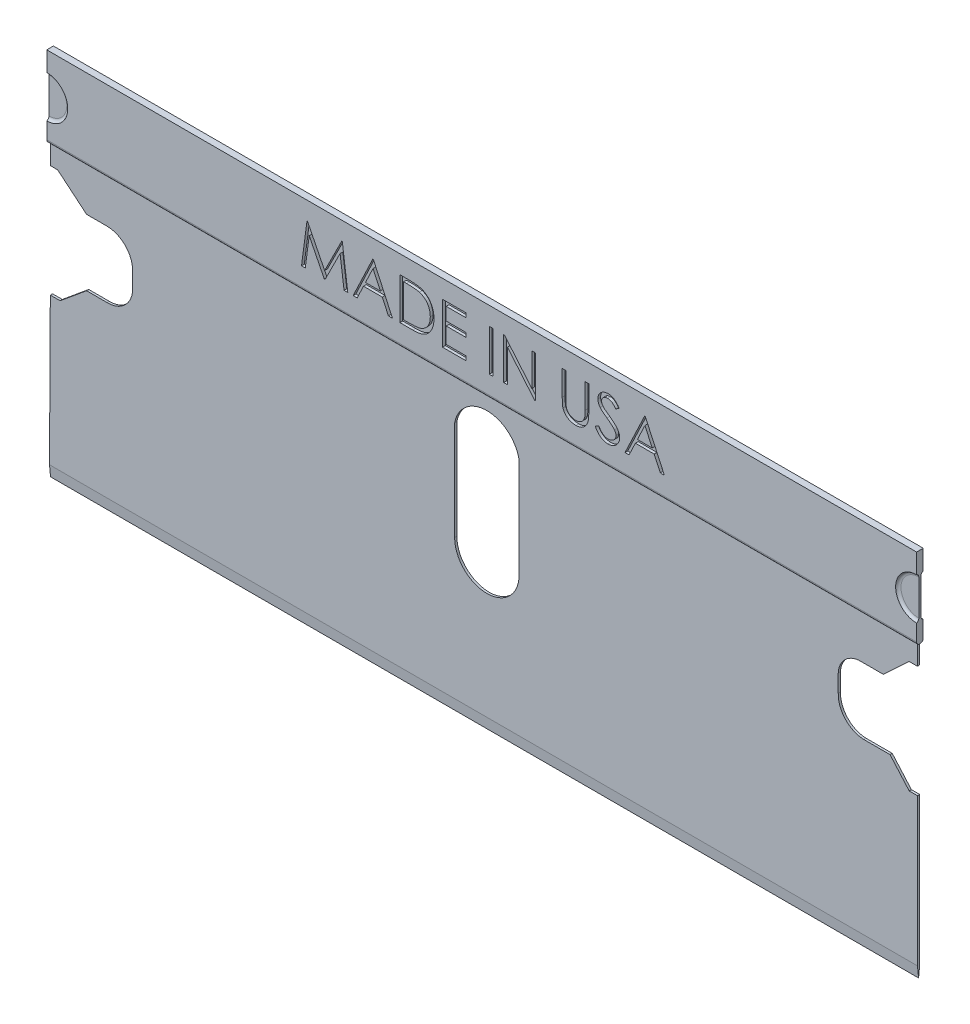
SolidWorks part; units mm, degrees
ref_plane "Front Plane" through (0, 0, 0) normal (0, 0, 1) x (1, 0, 0)
ref_plane "Top Plane" through (0, 0, 0) normal (0, 1, 0) x (1, 0, 0)
ref_plane "Right Plane" through (0, 0, 0) normal (1, 0, 0) x (0, 0, -1)
sketch "Sketch1" plane through (0, 0, 0) normal (0, 0, 1) x (1, 0, 0)
  line L0 (68.5, 98.5) -> (342.5, 98.5) construction
  line L1 (6.6432, 0) -> (405.0953, 0)
  line L2 (405.0953, 0) -> (405.0953, 72.7175)
  line L3 (392.4917, 82.7561) -> (380.4108, 82.7561)
  line L4 (368.7248, 95.2868) -> (368.7248, 103.2753)
  line L5 (379.511, 113.1269) -> (389.4487, 113.1269)
  line L6 (405.0953, 72.7175) -> (401.3011, 72.7175)
  line L7 (405.0953, 124.1749) -> (401.3011, 124.1749)
  line L8 (405.0953, 124.1749) -> (405.0953, 133.9462)
  line L9 (405.0953, 133.9462) -> (7.043, 133.9462)
  line L10 (7.043, 133.9462) -> (7.043, 124.1749)
  line L11 (7.043, 124.1749) -> (10.404, 124.1749)
  line L12 (23.6907, 113.1269) -> (33.0176, 113.1269)
  line L13 (44.8608, 101.2782) -> (44.8608, 93.9286)
  line L14 (33.0176, 82.7561) -> (23.6907, 82.7561)
  line L15 (10.404, 124.1749) -> (23.6907, 113.1269)
  line L16 (23.6907, 82.7561) -> (11.5392, 72.7175)
  line L17 (11.5392, 72.7175) -> (7.043, 72.7175)
  line L18 (7.043, 72.7175) -> (6.6432, 0)
  line L19 (192.6406, 114.6996) -> (192.6406, 69.1011)
  line L20 (222.2574, 114.6996) -> (222.2574, 69.1011)
  line L21 (401.3011, 124.1749) -> (389.4487, 113.1269)
  line L22 (401.3011, 72.7175) -> (392.4917, 82.7561)
  arc A0 (33.0176, 113.1269) -> (44.8608, 101.2782) centre (33.0176, 101.2838) cw
  arc A1 (380.4108, 82.7561) -> (368.7248, 95.2868) centre (380.8331, 94.8645) cw
  arc A2 (368.7248, 103.2753) -> (379.511, 113.1269) centre (379.0437, 102.8081) cw
  arc A3 (44.8608, 93.9286) -> (33.0176, 82.7561) centre (33.353, 94.2639) cw
  arc A4 (192.6406, 114.6996) -> (222.2574, 114.6996) centre (207.449, 111.9289) cw
  arc A5 (192.6406, 69.1011) -> (222.2574, 69.1011) centre (207.449, 69.1011) ccw
extrude "Boss-Extrude1" add sketch "Sketch1" along normal blind 0.508 and the other way blind 0.508
chamfer "Chamfer1" distance 0.508 distance2 5.08 1 edges at (205.8693, 0, 0.508) first distance on face at (205.8693, 0, 0)
chamfer "Chamfer2" distance 5.08 distance2 0.508 1 edges at (205.8693, 0, -0.508) first distance on face at (207.449, 91.2719, -0.508)
sketch "Sketch2" plane through (0, 0, 0.508) normal (0, 0, 1) x (1, 0, 0)
  line L0 (6.4329, 133.1394) -> (405.7054, 133.1394)
  line L2 (6.4329, 133.1394) -> (6.4329, 170.403)
  line L3 (405.7054, 170.403) -> (6.4329, 170.403)
  line L4 (405.7054, 133.1394) -> (405.7054, 170.403)
extrude "Boss-Extrude2" add sketch "Sketch2" along normal blind 1.016 and the other way blind 2.032
sketch "Sketch3" plane through (0, 0, 1.524) normal (0, 0, 1) x (1, 0, 0)
  line L0 (405.7054, 133.1394) -> (405.7054, 170.403) construction
  line L1 (405.7054, 161.3903) -> (405.7054, 142.1522)
  line L4 (6.4329, 161.3903) -> (6.4329, 142.1522)
  arc A0 (405.7054, 161.3903) -> (405.7054, 142.1522) centre (405.7054, 151.7712) ccw
  arc A1 (6.4329, 161.3903) -> (6.4329, 142.1522) centre (6.4329, 151.7712) cw
extrude "Cut-Extrude1" cut sketch "Sketch3" against normal up to surface (1.016 mm away) up to face at (206.4712, 93.3802, 0.508)
fillet "Fillet1" radius 1.524 2 edges at (16.052, 151.7712, 0.508) (396.0864, 151.7712, 0.508)
sketch "Sketch4" plane through (0, 0, -1.524) normal (0, 0, -1) x (-1, 0, 0)
  line L0 (-405.7054, 161.3903) -> (-405.7054, 142.1522)
  line L1 (-206.0692, 170.403) -> (-206.0692, 161.3903)
  line L2 (-405.7054, 170.403) -> (-6.4329, 170.403) construction
  line L3 (-6.4329, 161.3903) -> (-6.4329, 142.1522)
  arc A0 (-405.7054, 161.3903) -> (-405.7054, 142.1522) centre (-405.7054, 151.7712) cw
  arc A1 (-6.4329, 161.3903) -> (-6.4329, 142.1522) centre (-6.4329, 151.7712) ccw
  line M1 (-6.4329, 133.1394) -> (-6.4329, 170.403)
  line M3 (-405.7054, 170.403) -> (-405.7054, 133.1394)
extrude "Cut-Extrude2" cut sketch "Sketch4" against normal up to surface (1.016 mm away) contours A0 M3 | A1 M1 region at (401.6229, 151.7712, -1.524) region at (10.5154, 151.7712, -1.524) up to face at (206.4712, 93.3802, -0.508)
fillet "Fillet2" radius 1.524 2 edges at (16.052, 151.7712, -0.508) (396.0864, 151.7712, -0.508)
fillet "Fillet3" radius 1.524 2 edges at (206.0692, 133.1394, 1.524) (206.0692, 133.1394, -1.524)
sketch "Sketch5" plane through (0, 0, 1.524) normal (0, 0, 1) x (1, 0, 0)
  text T0 "MADE IN USA" font "Century Gothic" height in points 72
extrude "Cut-Extrude3" cut sketch "Sketch5" against normal blind 1.27
